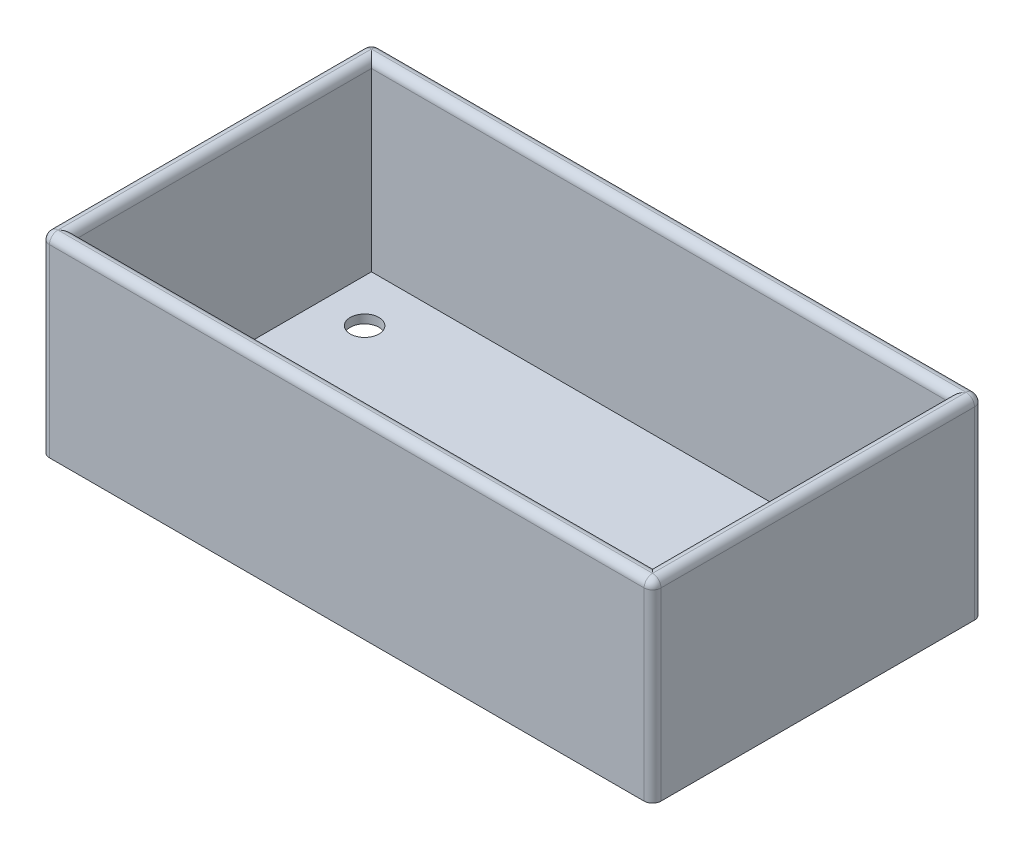
SolidWorks part; units mm, degrees
ref_plane "Front Plane" through (0, 0, 0) normal (0, 0, 1) x (1, 0, 0)
ref_plane "Top Plane" through (0, 0, 0) normal (0, 1, 0) x (1, 0, 0)
ref_plane "Right Plane" through (0, 0, 0) normal (1, 0, 0) x (0, 0, -1)
sketch "Sketch1" plane through (0, 0, 0) normal (0, 1, 0) x (1, 0, 0)
  line L1 (0, 0) -> (72.39, 0)
  line L2 (0, 0) -> (0, 39.116)
  line L3 (0, 39.116) -> (72.39, 39.116)
  line L4 (72.39, 0) -> (72.39, 39.116)
  dimension "D1" = 72.39
  dimension "D2" = 39.116
extrude "Boss-Extrude1" add sketch "Sketch1" along normal blind 22.86
sketch "Sketch2" plane through (0, 22.86, 0) normal (0, 1, 0) x (1, 0, 0)
  line L0 (0, 0) -> (72.39, 0) construction
  line L1 (2, 2) -> (70.39, 2)
  line L2 (2, 2) -> (2, 37.116)
  line L3 (2, 37.116) -> (70.39, 37.116)
  line L4 (70.39, 2) -> (70.39, 37.116)
  line L5 (0, 39.116) -> (0, 0) construction
  line L6 (72.39, 0) -> (72.39, 39.116) construction
  line L7 (72.39, 39.116) -> (0, 39.116) construction
  point P4 (36.195, 2)
  dimension "D1" = 2
  dimension "D2" = 2
  dimension "D3" = 2
  dimension "D4" = 2
extrude "Cut-Extrude1" cut sketch "Sketch2" against normal blind 21.844 contours L2 L1 L4 L3
fillet "Fillet1" radius 1 12 edges at (36.195, 22.86, -39.116) (72.39, 22.86, -19.558) (36.195, 22.86, 0) (0, 22.86, -19.558) (70.39, 22.86, -19.558) (36.195, 22.86, -37.116) (2, 22.86, -19.558) (36.195, 22.86, -2) (72.39, 11.43, 0) (72.39, 11.43, -39.116) (0, 11.43, 0) (0, 11.43, -39.116)
hole_wizard "M3 Clearance Hole1" positions "Sketch5" profile "Sketch6" hole size "M3" standard "ANSI Metric" end condition through all
sketch "Sketch5" plane through (0, 1.016, 0) normal (0, 1, 0) x (1, 0, 0)
  point P0 (7.1189, 31.1852)
  point P2 (7.1189, 7.1852)
  point P4 (65.1189, 31.1852)
  point P6 (65.1189, 7.1852)
  dimension "D1" = 24
  dimension "D2" = 24
  dimension "D3" = 58
  dimension "D4" = 58
sketch "Sketch6" plane through (7.1189, 1.016, -31.1852) normal (1, 0, 0) x (0, 0, 1)
  line L0 (0, 0) -> (0, 1.016)
  line L1 (0, 1.016) -> (1.7, 1.016)
  line L2 (1.7, 1.016) -> (1.7, 0)
  line L5 (1.7, 0) -> (0, 0)
  line L11 (0, -6.35) -> (0, 107.95) construction
  dimension "Thru Hole Dia." = 3.4
  dimension "Thru Hole Depth" = 1.016
